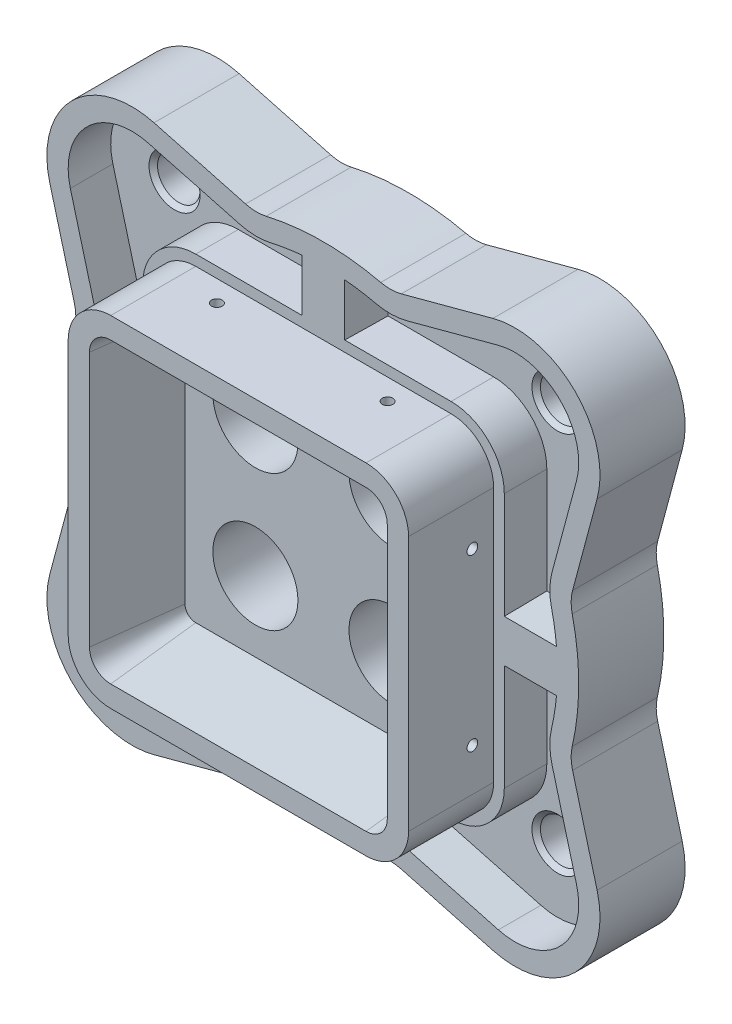
SolidWorks part; units mm, degrees
note: '?' marks a value the reader was unsure of.
ref_plane "Plane1" through (0, 0, 0) normal (0, 0, 1) x (1, 0, 0)
ref_plane "Plane2" through (0, 0, 0) normal (0, 1, 0) x (1, 0, 0)
ref_plane "Plane3" through (0, 0, 0) normal (1, 0, 0) x (0, 0, -1)
sketch "Sketch1" plane through (0, 0, 0) normal (0, 0, 1) x (1, 0, 0)
  line L0 (-50.576, 81.6845) -> (-23.2496, 74.3624)
  line L1 (-81.6845, 50.576) -> (-74.3624, 23.2496)
  line L2 (50.576, 81.6845) -> (23.2496, 74.3624)
  line L3 (81.6845, 50.576) -> (74.3624, 23.2496)
  line L4 (81.6845, -50.576) -> (74.3624, -23.2496)
  line L5 (50.576, -81.6845) -> (23.2496, -74.3624)
  line L6 (-50.576, -81.6845) -> (-23.2496, -74.3624)
  line L7 (-81.6845, -50.576) -> (-74.3624, -23.2496)
  line L8 (0, 0) -> (104.9579, 0) construction
  line L9 (0, 0) -> (0, 106.055) construction
  arc A0 (17.1108, 74.254) -> (-17.1108, 74.254) centre (0, 0) ccw
  arc A1 (81.6845, 50.576) -> (50.576, 81.6845) centre (57.15, 57.15) ccw
  arc A2 (-50.576, 81.6845) -> (-81.6845, 50.576) centre (-57.15, 57.15) ccw
  arc A3 (-81.6845, -50.576) -> (-50.576, -81.6845) centre (-57.15, -57.15) ccw
  arc A4 (50.576, -81.6845) -> (81.6845, -50.576) centre (57.15, -57.15) ccw
  arc A5 (74.254, -17.1108) -> (74.254, 17.1108) centre (0, 0) ccw
  arc A6 (-17.1108, -74.254) -> (17.1108, -74.254) centre (0, 0) ccw
  arc A7 (-74.254, 17.1108) -> (-74.254, -17.1108) centre (0, 0) ccw
  arc A8 (-17.1108, 74.254) -> (-23.2496, 74.3624) centre (-19.9626, 86.6297) cw
  arc A9 (17.1108, 74.254) -> (23.2496, 74.3624) centre (19.9626, 86.6297) ccw
  arc A10 (74.254, 17.1108) -> (74.3624, 23.2496) centre (86.6297, 19.9626) cw
  arc A11 (74.254, -17.1108) -> (74.3624, -23.2496) centre (86.6297, -19.9626) ccw
  arc A12 (17.1108, -74.254) -> (23.2496, -74.3624) centre (19.9626, -86.6297) cw
  arc A13 (-17.1108, -74.254) -> (-23.2496, -74.3624) centre (-19.9626, -86.6297) ccw
  arc A14 (-74.254, -17.1108) -> (-74.3624, -23.2496) centre (-86.6297, -19.9626) cw
  arc A15 (-74.254, 17.1108) -> (-74.3624, 23.2496) centre (-86.6297, 19.9626) ccw
  dimension "D1" = 152.4
  dimension "D2" = 75
  dimension "D11" = 25.4
  dimension "D12" = 12.7
  dimension "D3" = 57.15
  dimension "D4" = 57.15
  dimension "D5" = 57.15
  dimension "D6" = 57.15
  dimension "D7" = 60
  dimension "D8" = 60
  dimension "D9" = 60
  dimension "D10" = 60
  dimension "D13" = 75
  dimension "D14" = 75
  dimension "D15" = 75
extrude "Base-Extrude" add sketch "Sketch1" along normal blind 25.4
sketch "Sketch2" plane through (0, 0, 25.4) normal (0, 0, 1) x (1, 0, 0)
  line L1 (-38.1, 50.8) -> (38.1, 50.8)
  line L2 (-50.8, 38.1) -> (-50.8, -38.1)
  line L3 (-38.1, -50.8) -> (38.1, -50.8)
  line L4 (50.8, 38.1) -> (50.8, -38.1)
  arc A0 (-50.8, 38.1) -> (-38.1, 50.8) centre (-38.1, 38.1) cw
  arc A1 (50.8, 38.1) -> (38.1, 50.8) centre (38.1, 38.1) ccw
  arc A2 (50.8, -38.1) -> (38.1, -50.8) centre (38.1, -38.1) cw
  arc A3 (-38.1, -50.8) -> (-50.8, -38.1) centre (-38.1, -38.1) cw
  point P7 (-50.8, 50.8)
  point P10 (50.8, 50.8)
  point P13 (50.8, -50.8)
  dimension "D5" = 12.7
  dimension "D1" = 101.6
  dimension "D2" = 101.6
  dimension "D3" = 50.8
  dimension "D4" = 50.8
extrude "Boss-Extrude1" add sketch "Sketch2" along normal blind 25.4
sketch "Sketch3" plane through (0, 0, 50.8) normal (0, 0, 1) x (1, 0, 0)
  line L8 (-44.45, 38.1) -> (-44.45, -38.1)
  line L9 (-38.1, -44.45) -> (38.1, -44.45)
  line L10 (44.45, -38.1) -> (44.45, 38.1)
  line L11 (38.1, 44.45) -> (-38.1, 44.45)
  line L12 (-44.45, 38.1) -> (-44.45, -38.1)
  line L13 (-38.1, -44.45) -> (38.1, -44.45)
  line L14 (44.45, -38.1) -> (44.45, 38.1)
  line L15 (38.1, 44.45) -> (-38.1, 44.45)
  arc A8 (-38.1, 44.45) -> (-44.45, 38.1) centre (-38.1, 38.1) ccw
  arc A9 (-44.45, -38.1) -> (-38.1, -44.45) centre (-38.1, -38.1) ccw
  arc A10 (38.1, -44.45) -> (44.45, -38.1) centre (38.1, -38.1) ccw
  arc A11 (44.45, 38.1) -> (38.1, 44.45) centre (38.1, 38.1) ccw
  arc A12 (-38.1, 44.45) -> (-44.45, 38.1) centre (-38.1, 38.1) ccw
  arc A13 (-44.45, -38.1) -> (-38.1, -44.45) centre (-38.1, -38.1) ccw
  arc A14 (38.1, -44.45) -> (44.45, -38.1) centre (38.1, -38.1) ccw
  arc A15 (44.45, 38.1) -> (38.1, 44.45) centre (38.1, 38.1) ccw
  dimension "D1" = 6.35
extrude "Cut-Extrude1" cut sketch "Sketch3" against normal blind 25.4 draft 7
sketch "Sketch4" plane through (0, 0, 25.4) normal (0, 0, 1) x (1, 0, 0)
  circle A0 centre (-20.32, 20.32) radius 12.7
  circle A1 centre (20.32, 20.32) radius 12.7
  circle A2 centre (20.32, -20.32) radius 12.7
  circle A3 centre (-20.32, -20.32) radius 12.7
  dimension "D1" = 25.4
  dimension "D2" = 20.32
  dimension "D3" = 20.32
  dimension "D4" = 20.32
  dimension "D5" = 20.32
extrude "Cut-Extrude2" cut sketch "Sketch4" against normal through all
sketch "Sketch5" plane through (0, 0, 25.4) normal (0, 0, 1) x (1, 0, 0)
  line L16 (-75.5509, 52.2195) -> (-68.2288, 24.8931)
  line L17 (-68.2288, -24.8931) -> (-75.5509, -52.2195)
  line L18 (-52.2195, -75.5509) -> (-24.8931, -68.2288)
  line L19 (24.8931, -68.2288) -> (52.2195, -75.5509)
  line L20 (75.5509, -52.2195) -> (68.2288, -24.8931)
  line L21 (68.2288, 24.8931) -> (75.5509, 52.2195)
  line L22 (52.2195, 75.5509) -> (24.8931, 68.2288)
  line L23 (-24.8931, 68.2288) -> (-52.2195, 75.5509)
  line L24 (-75.5509, 52.2195) -> (-68.2288, 24.8931)
  line L25 (-68.2288, -24.8931) -> (-75.5509, -52.2195)
  line L26 (-52.2195, -75.5509) -> (-24.8931, -68.2288)
  line L27 (24.8931, -68.2288) -> (52.2195, -75.5509)
  line L28 (75.5509, -52.2195) -> (68.2288, -24.8931)
  line L29 (68.2288, 24.8931) -> (75.5509, 52.2195)
  line L30 (52.2195, 75.5509) -> (24.8931, 68.2288)
  line L31 (-24.8931, 68.2288) -> (-52.2195, 75.5509)
  line L48 (-53.975, 38.1) -> (-53.975, -38.1)
  line L49 (38.1, 53.975) -> (-38.1, 53.975)
  line L50 (53.975, -38.1) -> (53.975, 38.1)
  line L51 (-38.1, -53.975) -> (38.1, -53.975)
  line L52 (-53.975, 38.1) -> (-53.975, -38.1)
  line L53 (38.1, 53.975) -> (-38.1, 53.975)
  line L54 (53.975, -38.1) -> (53.975, 38.1)
  line L55 (-38.1, -53.975) -> (38.1, -53.975)
  arc A33 (-52.2195, 75.5509) -> (-75.5509, 52.2195) centre (-57.15, 57.15) ccw
  arc A34 (-68.0662, 15.6849) -> (-68.2288, 24.8931) centre (-86.6297, 19.9626) ccw
  arc A35 (-68.0662, 15.6849) -> (-68.0662, -15.6849) centre (0, 0) ccw
  arc A36 (-68.2288, -24.8931) -> (-68.0662, -15.6849) centre (-86.6297, -19.9626) ccw
  arc A37 (-75.5509, -52.2195) -> (-52.2195, -75.5509) centre (-57.15, -57.15) ccw
  arc A38 (-15.6849, -68.0662) -> (-24.8931, -68.2288) centre (-19.9626, -86.6297) ccw
  arc A39 (-15.6849, -68.0662) -> (15.6849, -68.0662) centre (0, 0) ccw
  arc A40 (24.8931, -68.2288) -> (15.6849, -68.0662) centre (19.9626, -86.6297) ccw
  arc A41 (52.2195, -75.5509) -> (75.5509, -52.2195) centre (57.15, -57.15) ccw
  arc A42 (68.0662, -15.6849) -> (68.2288, -24.8931) centre (86.6297, -19.9626) ccw
  arc A43 (68.0662, -15.6849) -> (68.0662, 15.6849) centre (0, 0) ccw
  arc A44 (68.2288, 24.8931) -> (68.0662, 15.6849) centre (86.6297, 19.9626) ccw
  arc A45 (75.5509, 52.2195) -> (52.2195, 75.5509) centre (57.15, 57.15) ccw
  arc A46 (15.6849, 68.0662) -> (24.8931, 68.2288) centre (19.9626, 86.6297) ccw
  arc A47 (15.6849, 68.0662) -> (-15.6849, 68.0662) centre (0, 0) ccw
  arc A48 (-24.8931, 68.2288) -> (-15.6849, 68.0662) centre (-19.9626, 86.6297) ccw
  arc A49 (-52.2195, 75.5509) -> (-75.5509, 52.2195) centre (-57.15, 57.15) ccw
  arc A50 (-68.0662, 15.6849) -> (-68.2288, 24.8931) centre (-86.6297, 19.9626) ccw
  arc A51 (-68.0662, 15.6849) -> (-68.0662, -15.6849) centre (0, 0) ccw
  arc A52 (-68.2288, -24.8931) -> (-68.0662, -15.6849) centre (-86.6297, -19.9626) ccw
  arc A53 (-75.5509, -52.2195) -> (-52.2195, -75.5509) centre (-57.15, -57.15) ccw
  arc A54 (-15.6849, -68.0662) -> (-24.8931, -68.2288) centre (-19.9626, -86.6297) ccw
  arc A55 (-15.6849, -68.0662) -> (15.6849, -68.0662) centre (0, 0) ccw
  arc A56 (24.8931, -68.2288) -> (15.6849, -68.0662) centre (19.9626, -86.6297) ccw
  arc A57 (52.2195, -75.5509) -> (75.5509, -52.2195) centre (57.15, -57.15) ccw
  arc A58 (68.0662, -15.6849) -> (68.2288, -24.8931) centre (86.6297, -19.9626) ccw
  arc A59 (68.0662, -15.6849) -> (68.0662, 15.6849) centre (0, 0) ccw
  arc A60 (68.2288, 24.8931) -> (68.0662, 15.6849) centre (86.6297, 19.9626) ccw
  arc A61 (75.5509, 52.2195) -> (52.2195, 75.5509) centre (57.15, 57.15) ccw
  arc A62 (15.6849, 68.0662) -> (24.8931, 68.2288) centre (19.9626, 86.6297) ccw
  arc A63 (15.6849, 68.0662) -> (-15.6849, 68.0662) centre (0, 0) ccw
  arc A64 (-24.8931, 68.2288) -> (-15.6849, 68.0662) centre (-19.9626, 86.6297) ccw
  arc A69 (-53.975, -38.1) -> (-38.1, -53.975) centre (-38.1, -38.1) ccw
  arc A70 (-38.1, 53.975) -> (-53.975, 38.1) centre (-38.1, 38.1) ccw
  arc A71 (53.975, 38.1) -> (38.1, 53.975) centre (38.1, 38.1) ccw
  arc A72 (38.1, -53.975) -> (53.975, -38.1) centre (38.1, -38.1) ccw
  arc A73 (-53.975, -38.1) -> (-38.1, -53.975) centre (-38.1, -38.1) ccw
  arc A74 (-38.1, 53.975) -> (-53.975, 38.1) centre (-38.1, 38.1) ccw
  arc A75 (53.975, 38.1) -> (38.1, 53.975) centre (38.1, 38.1) ccw
  arc A76 (38.1, -53.975) -> (53.975, -38.1) centre (38.1, -38.1) ccw
  dimension "D1" = 6.35
  dimension "D2" = 3.175
extrude "Cut-Extrude3" cut sketch "Sketch5" against normal blind 12.7
sketch "Sketch6" plane through (0, 0, 25.4) normal (0, 0, 1) x (1, 0, 0)
  line L0 (50.8, -38.1) -> (50.8, 38.1) construction
  line L1 (50.8, 6.35) -> (75.935, 6.35)
  line L2 (50.8, 6.35) -> (50.8, -6.35)
  line L3 (50.8, -6.35) -> (75.935, -6.35)
  line L4 (75.935, 6.35) -> (75.935, -6.35)
  line L6 (50, 0) -> (-50, 0) construction
  arc A0 (74.254, -17.1108) -> (74.254, 17.1108) centre (0, 0) ccw construction
  dimension "D1" = 12.7
  dimension "D2" = 6.35
extrude "Boss-Extrude2" add sketch "Sketch6" along normal up to surface (12.7 mm away)
ref_axis "Axis1" through (0, 0, -50) along (0, 0, 1)?
pattern_circular "CirPattern1" count 4 every 90 about axis through (0, 0, 0) along (0, 0, 1) of "Boss-Extrude2"
sketch "Sketch7" plane through (0, 0, 12.7) normal (0, 0, 1) x (1, 0, 0)
  circle A0 centre (57.15, 57.15) radius 6.35
  circle A1 centre (-57.15, 57.15) radius 6.35
  circle A2 centre (-57.15, -57.15) radius 6.35
  circle A3 centre (57.15, -57.15) radius 6.35
  arc A4 (81.6845, 50.576) -> (50.576, 81.6845) centre (57.15, 57.15) ccw construction
  arc A5 (-50.576, 81.6845) -> (-81.6845, 50.576) centre (-57.15, 57.15) ccw construction
  arc A6 (-81.6845, -50.576) -> (-50.576, -81.6845) centre (-57.15, -57.15) ccw construction
  arc A7 (50.576, -81.6845) -> (81.6845, -50.576) centre (57.15, -57.15) ccw construction
  dimension "D1" = 12.7
extrude "Cut-Extrude4" cut sketch "Sketch7" against normal through all and the other way blind 12.7
draft "Draft1" type of draft neutral plane draft angle 1 faces to draft 8 face at (61.7679, 6.35, 19.05) face at (6.35, 61.7679, 19.05) face at (-6.35, 61.7679, 19.05) face at (-61.7679, 6.35, 19.05) face at (-61.7679, -6.35, 19.05) face at (-6.35, -61.7679, 19.05) face at (6.35, -61.7679, 19.05) face at (61.7679, -6.35, 19.05) neutral plane through (-57.15, 57.15, 25.4) neutral plane normal (0, 0, 1) parameters "D1"=1
chamfer "Chamfer1" distance 1.27 angle 45 8 edges at (63.5, 57.15, 12.7) (63.5, 57.15, 0) (-50.8, 57.15, 12.7) (-50.8, 57.15, 0) (-50.8, -57.15, 12.7) (-50.8, -57.15, 0) (63.5, -57.15, 12.7) (63.5, -57.15, 0)
hole_wizard "Hole1" positions "Sketch10" profile "Sketch9" legacy
sketch "Sketch10" plane through (0, -50.8, 0) normal (0, -1, 0) x (1, 0, 0)
  line L0 (-38.1, 50.8) -> (-38.1, 25.4) construction
  line L1 (-50.576, 25.4) -> (-23.2496, 25.4) construction
  point P0 (-25.4, 31.75)
  dimension "D1" = 12.7
  dimension "D2" = 6.35
sketch "Sketch9" plane through (-25.4, -50.8, 31.75) normal (1, 0, 0) x (0, 0, -1)
  line L0 (0, 0) -> (0, 6.0339)
  line L1 (0, 6.0339) -> (1.5875, 5.08)
  line L2 (1.5875, 5.08) -> (1.5875, 0)
  line L4 (1.5875, 0) -> (0, 0)
  line L6 (0, 6.0339) -> (-1.5875, 5.08) construction
  line L7 (0, -4.2442) -> (0, 117.3081) construction
  dimension "Diameter" = 3.175
  dimension "Depth" = 5.08
  dimension "Drill Angle" = 118
hole_wizard "Hole2" positions "Sketch12" profile "Sketch11" legacy
sketch "Sketch12" plane through (0, -50.8, 0) normal (0, -1, 0) x (1, 0, 0)
  line L0 (38.1, 50.8) -> (38.1, 25.4) construction
  line L1 (23.2496, 25.4) -> (50.576, 25.4) construction
  point P0 (25.4, 31.75)
  dimension "D1" = 12.7
  dimension "D2" = 6.35
sketch "Sketch11" plane through (25.4, -50.8, 31.75) normal (1, 0, 0) x (0, 0, -1)
  line L0 (0, 0) -> (0, 6.0339)
  line L1 (0, 6.0339) -> (1.5875, 5.08)
  line L2 (1.5875, 5.08) -> (1.5875, 0)
  line L4 (1.5875, 0) -> (0, 0)
  line L6 (0, 6.0339) -> (-1.5875, 5.08) construction
  line L7 (0, -4.2442) -> (0, 117.3081) construction
  dimension "Diameter" = 3.175
  dimension "Depth" = 5.08
  dimension "Drill Angle" = 118
hole_wizard "Hole3" positions "Sketch14" profile "Sketch13" legacy
sketch "Sketch14" plane through (-50.8, 0, 0) normal (-1, 0, 0) x (0, 0, 1)
  line L0 (50.8, 38.1) -> (25.4, 38.1) construction
  line L1 (25.4, 50.576) -> (25.4, 23.2496) construction
  point P0 (31.75, 25.4)
  dimension "D1" = 12.7
  dimension "D2" = 6.35
sketch "Sketch13" plane through (-50.8, 25.4, 31.75) normal (0, 1, 0) x (0, 0, 1)
  line L0 (0, 0) -> (0, 6.0339)
  line L1 (0, 6.0339) -> (1.5875, 5.08)
  line L2 (1.5875, 5.08) -> (1.5875, 0)
  line L4 (1.5875, 0) -> (0, 0)
  line L6 (0, 6.0339) -> (-1.5875, 5.08) construction
  line L7 (0, -4.2442) -> (0, 117.3081) construction
  dimension "Diameter" = 3.175
  dimension "Depth" = 5.08
  dimension "Drill Angle" = 118
hole_wizard "Hole4" positions "Sketch16" profile "Sketch15" legacy
sketch "Sketch16" plane through (-50.8, 0, 0) normal (-1, 0, 0) x (0, 0, 1)
  line L0 (50.8, -38.1) -> (25.4, -38.1) construction
  line L1 (25.4, -23.2496) -> (25.4, -50.576) construction
  point P0 (31.75, -25.4)
  dimension "D1" = 12.7
  dimension "D2" = 6.35
sketch "Sketch15" plane through (-50.8, -25.4, 31.75) normal (0, 1, 0) x (0, 0, 1)
  line L0 (0, 0) -> (0, 6.0339)
  line L1 (0, 6.0339) -> (1.5875, 5.08)
  line L2 (1.5875, 5.08) -> (1.5875, 0)
  line L4 (1.5875, 0) -> (0, 0)
  line L6 (0, 6.0339) -> (-1.5875, 5.08) construction
  line L7 (0, -4.2442) -> (0, 117.3081) construction
  dimension "Diameter" = 3.175
  dimension "Depth" = 5.08
  dimension "Drill Angle" = 118
hole_wizard "Hole5" positions "Sketch19" profile "Sketch18" legacy
sketch "Sketch19" plane through (50.8, 0, 0) normal (1, 0, 0) x (0, 0, -1)
  line L0 (-50.8, -38.1) -> (-25.4, -38.1) construction
  line L1 (-25.4, -50.576) -> (-25.4, -23.2496) construction
  point P0 (-31.75, -25.4)
  dimension "D1" = 12.7
  dimension "D2" = 6.35
sketch "Sketch18" plane through (50.8, -25.4, 31.75) normal (0, 1, 0) x (0, 0, -1)
  line L0 (0, 0) -> (0, 6.0339)
  line L1 (0, 6.0339) -> (1.5875, 5.08)
  line L2 (1.5875, 5.08) -> (1.5875, 0)
  line L4 (1.5875, 0) -> (0, 0)
  line L6 (0, 6.0339) -> (-1.5875, 5.08) construction
  line L7 (0, -4.2442) -> (0, 117.3081) construction
  dimension "Diameter" = 3.175
  dimension "Depth" = 5.08
  dimension "Drill Angle" = 118
hole_wizard "Hole6" positions "Sketch21" profile "Sketch20" legacy
sketch "Sketch21" plane through (50.8, 0, 0) normal (1, 0, 0) x (0, 0, -1)
  line L0 (-50.8, 38.1) -> (-25.4, 38.1) construction
  line L1 (-25.4, 23.2496) -> (-25.4, 50.576) construction
  point P0 (-31.75, 25.4)
  dimension "D1" = 12.7
  dimension "D2" = 6.35
sketch "Sketch20" plane through (50.8, 25.4, 31.75) normal (0, 1, 0) x (0, 0, -1)
  line L0 (0, 0) -> (0, 6.0339)
  line L1 (0, 6.0339) -> (1.5875, 5.08)
  line L2 (1.5875, 5.08) -> (1.5875, 0)
  line L4 (1.5875, 0) -> (0, 0)
  line L6 (0, 6.0339) -> (-1.5875, 5.08) construction
  line L7 (0, -4.2442) -> (0, 117.3081) construction
  dimension "Diameter" = 3.175
  dimension "Depth" = 5.08
  dimension "Drill Angle" = 118
hole_wizard "Hole7" positions "Sketch23" profile "Sketch22" legacy
sketch "Sketch23" plane through (0, 50.8, 0) normal (0, 1, 0) x (-1, 0, 0)
  line L0 (-38.1, 50.8) -> (-38.1, 25.4) construction
  line L1 (-38.1, 25.4) -> (-6.35, 25.4) construction
  point P0 (-25.4, 31.6566)
  dimension "D1" = 12.7
  dimension "D2" = 6.2566
sketch "Sketch22" plane through (25.4, 50.8, 31.6566) normal (1, 0, 0) x (0, 0, 1)
  line L0 (0, 0) -> (0, 6.0339)
  line L1 (0, 6.0339) -> (1.5875, 5.08)
  line L2 (1.5875, 5.08) -> (1.5875, 0)
  line L4 (1.5875, 0) -> (0, 0)
  line L6 (0, 6.0339) -> (-1.5875, 5.08) construction
  line L7 (0, -4.2442) -> (0, 117.3081) construction
  dimension "Diameter" = 3.175
  dimension "Depth" = 5.08
  dimension "Drill Angle" = 118
hole_wizard "Hole8" positions "Sketch25" profile "Sketch24" legacy
sketch "Sketch25" plane through (0, 50.8, 0) normal (0, 1, 0) x (-1, 0, 0)
  line L0 (38.1, 50.8) -> (38.1, 25.4) construction
  line L1 (6.35, 25.4) -> (38.1, 25.4) construction
  point P0 (25.4526, 31.75)
  dimension "D1" = 12.6474
  dimension "D2" = 6.35
sketch "Sketch24" plane through (-25.4526, 50.8, 31.75) normal (1, 0, 0) x (0, 0, 1)
  line L0 (0, 0) -> (0, 6.0339)
  line L1 (0, 6.0339) -> (1.5875, 5.08)
  line L2 (1.5875, 5.08) -> (1.5875, 0)
  line L4 (1.5875, 0) -> (0, 0)
  line L6 (0, 6.0339) -> (-1.5875, 5.08) construction
  line L7 (0, -4.2442) -> (0, 117.3081) construction
  dimension "Diameter" = 3.175
  dimension "Depth" = 5.08
  dimension "Drill Angle" = 118
sketch "Sketch17" plane through (0, 0, 0) normal (0, 0, -1) x (-1, 0, 0)
  circle A0 centre (0, 0) radius 50.8
  circle A1 centre (0, 0) radius 69.85
  dimension "D1" = 101.6
  dimension "D2" = 19.05
extrude "Cut-Extrude5" cut sketch "Sketch17" against normal blind 3.175
ref_plane "Plane4" through (0, 0, 12.7) normal (0, 0, -1) x (-1, 0, 0)
sketch "Sketch26" plane through (0, 0, 12.7) normal (0, 0, -1) x (-1, 0, 0)
  line L8 (50.576, 81.6845) -> (23.2496, 74.3624)
  line L9 (-23.2496, 74.3624) -> (-50.576, 81.6845)
  line L10 (-81.6845, 50.576) -> (-74.3624, 23.2496)
  line L11 (-74.3624, -23.2496) -> (-81.6845, -50.576)
  line L12 (-50.576, -81.6845) -> (-23.2496, -74.3624)
  line L13 (23.2496, -74.3624) -> (50.576, -81.6845)
  line L14 (81.6845, -50.576) -> (74.3624, -23.2496)
  line L15 (74.3624, 23.2496) -> (81.6845, 50.576)
  line L16 (50.576, 81.6845) -> (23.2496, 74.3624)
  line L17 (-23.2496, 74.3624) -> (-50.576, 81.6845)
  line L18 (-81.6845, 50.576) -> (-74.3624, 23.2496)
  line L19 (-74.3624, -23.2496) -> (-81.6845, -50.576)
  line L20 (-50.576, -81.6845) -> (-23.2496, -74.3624)
  line L21 (23.2496, -74.3624) -> (50.576, -81.6845)
  line L22 (81.6845, -50.576) -> (74.3624, -23.2496)
  line L23 (74.3624, 23.2496) -> (81.6845, 50.576)
  arc A16 (81.6845, 50.576) -> (50.576, 81.6845) centre (57.15, 57.15) ccw
  arc A17 (17.1108, 74.254) -> (23.2496, 74.3624) centre (19.9626, 86.6297) ccw
  arc A18 (17.1108, 74.254) -> (-17.1108, 74.254) centre (0, 0) ccw
  arc A19 (-23.2496, 74.3624) -> (-17.1108, 74.254) centre (-19.9626, 86.6297) ccw
  arc A20 (-50.576, 81.6845) -> (-81.6845, 50.576) centre (-57.15, 57.15) ccw
  arc A21 (-74.254, 17.1108) -> (-74.3624, 23.2496) centre (-86.6297, 19.9626) ccw
  arc A22 (-74.254, 17.1108) -> (-74.254, -17.1108) centre (0, 0) ccw
  arc A23 (-74.3624, -23.2496) -> (-74.254, -17.1108) centre (-86.6297, -19.9626) ccw
  arc A24 (-81.6845, -50.576) -> (-50.576, -81.6845) centre (-57.15, -57.15) ccw
  arc A25 (-17.1108, -74.254) -> (-23.2496, -74.3624) centre (-19.9626, -86.6297) ccw
  arc A26 (-17.1108, -74.254) -> (17.1108, -74.254) centre (0, 0) ccw
  arc A27 (23.2496, -74.3624) -> (17.1108, -74.254) centre (19.9626, -86.6297) ccw
  arc A28 (50.576, -81.6845) -> (81.6845, -50.576) centre (57.15, -57.15) ccw
  arc A29 (74.254, -17.1108) -> (74.3624, -23.2496) centre (86.6297, -19.9626) ccw
  arc A30 (74.254, -17.1108) -> (74.254, 17.1108) centre (0, 0) ccw
  arc A31 (74.3624, 23.2496) -> (74.254, 17.1108) centre (86.6297, 19.9626) ccw
  arc A32 (81.6845, 50.576) -> (50.576, 81.6845) centre (57.15, 57.15) ccw
  arc A33 (17.1108, 74.254) -> (23.2496, 74.3624) centre (19.9626, 86.6297) ccw
  arc A34 (17.1108, 74.254) -> (-17.1108, 74.254) centre (0, 0) ccw
  arc A35 (-23.2496, 74.3624) -> (-17.1108, 74.254) centre (-19.9626, 86.6297) ccw
  arc A36 (-50.576, 81.6845) -> (-81.6845, 50.576) centre (-57.15, 57.15) ccw
  arc A37 (-74.254, 17.1108) -> (-74.3624, 23.2496) centre (-86.6297, 19.9626) ccw
  arc A38 (-74.254, 17.1108) -> (-74.254, -17.1108) centre (0, 0) ccw
  arc A39 (-74.3624, -23.2496) -> (-74.254, -17.1108) centre (-86.6297, -19.9626) ccw
  arc A40 (-81.6845, -50.576) -> (-50.576, -81.6845) centre (-57.15, -57.15) ccw
  arc A41 (-17.1108, -74.254) -> (-23.2496, -74.3624) centre (-19.9626, -86.6297) ccw
  arc A42 (-17.1108, -74.254) -> (17.1108, -74.254) centre (0, 0) ccw
  arc A43 (23.2496, -74.3624) -> (17.1108, -74.254) centre (19.9626, -86.6297) ccw
  arc A44 (50.576, -81.6845) -> (81.6845, -50.576) centre (57.15, -57.15) ccw
  arc A45 (74.254, -17.1108) -> (74.3624, -23.2496) centre (86.6297, -19.9626) ccw
  arc A46 (74.254, -17.1108) -> (74.254, 17.1108) centre (0, 0) ccw
  arc A47 (74.3624, 23.2496) -> (74.254, 17.1108) centre (86.6297, 19.9626) ccw
  dimension "D1" = 0
sketch "Sketch27" plane through (0, 0, 0) normal (1, 0, 0) x (0, 0, -1)
  line L0 (-25.4, 82.55) -> (-25.4, 50.576) construction
  line L1 (-19.05, 91.44) -> (-6.35, 91.44)
  line L2 (-19.05, 91.44) -> (-19.05, 72.39)
  line L3 (-19.05, 72.39) -> (-6.35, 72.39)
  line L4 (-6.35, 91.44) -> (-6.35, 72.39)
  line L5 (50, 0) -> (-50, 0) construction
  dimension "D1" = 12.7
  dimension "D2" = 6.35
  dimension "D3" = 72.39
  dimension "D4" = 19.05
sweep "Keyway slot" [suppressed] cut profiles "Sketch27" path "Sketch26"
sketch "Sketch30" plane through (0, -50.8, 0) normal (0, -1, 0) x (1, 0, 0)
  line L0 (-38.1, 38.1) -> (38.1, 38.1)
  line L1 (-38.1, 50.8) -> (-38.1, 25.4) construction
  line L2 (38.1, 50.8) -> (38.1, 25.4) construction
sketch "SWCAM LOGO" plane through (0, -50.8, 0) normal (0, -1, 0) x (1, 0, 0)
  text T0 " SOLIDWORKSCAM" font "Century Gothic" height in points 22
